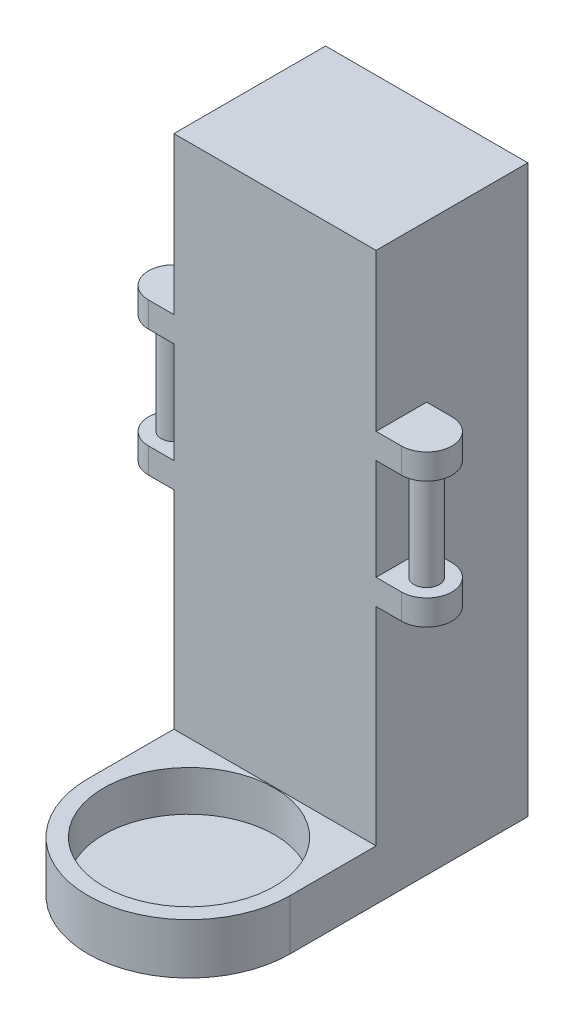
SolidWorks part; units mm, degrees
ref_plane "Front Plane" through (0, 0, 0) normal (0, 0, 1) x (1, 0, 0)
ref_plane "Top Plane" through (0, 0, 0) normal (0, 1, 0) x (1, 0, 0)
ref_plane "Right Plane" through (0, 0, 0) normal (1, 0, 0) x (0, 0, -1)
sketch "Sketch1" plane through (0, 0, 0) normal (0, 0, 1) x (1, 0, 0)
  line L1 (-25.4, -71.12) -> (25.4, -71.12)
  line L2 (-25.4, -71.12) -> (-25.4, 71.12)
  line L3 (-25.4, 71.12) -> (25.4, 71.12)
  line L4 (25.4, -71.12) -> (25.4, 71.12)
  line L5 (-25.4, -71.12) -> (25.4, 71.12) construction
  line L6 (-25.4, 71.12) -> (25.4, -71.12) construction
  point P0 (0, 0)
  dimension "D1" = 142.24
  dimension "D2" = 50.8
extrude "Boss-Extrude1" add sketch "Sketch1" along normal blind 38.1
sketch "Sketch8" plane through (0, -71.12, 0) normal (0, -1, 0) x (1, 0, 0)
  line L1 (-25.4, 38.1) -> (-25.4, 59.69)
  line L2 (25.4, 38.1) -> (25.4, 59.69)
  line L3 (-25.4, 38.1) -> (25.4, 38.1) construction
  line L4 (-25.4, 38.1) -> (25.4, 38.1)
  arc A0 (25.4, 59.69) -> (-25.4, 59.69) centre (0, 59.69) ccw
  circle A1 centre (0, 59.69) radius 21.4313
  dimension "D2" = 21.59
  dimension "D1" = 25.4
  dimension "D3" = 42.8625
extrude "Boss-Extrude2" add sketch "Sketch8" against normal blind 2.54 separate body contours L4 A1 L2 A0 L1 | A1 region at (-24.708, -71.12, 48.895) region at (0, -71.12, 59.69)
extrude "Boss-Extrude9" add sketch "Sketch8<5>" against normal blind 12.7 contours L2 A0 L1 L4 A1 region at (-24.708, -71.12, 48.895)
sketch "Sketch8<5>" plane through (0, -71.12, 0) normal (0, -1, 0) x (1, 0, 0) same geometry as "Sketch8"
sketch "Sketch18" plane through (0, 0, 38.1) normal (0, 0, 1) x (1, 0, 0)
  line L0 (0, -58.42) -> (0, 32.1084) construction
  line L1 (25.4, -58.42) -> (-25.4, -58.42) construction
sketch "Sketch19" plane through (-25.4, 0, 0) normal (-1, 0, 0) x (0, 0, 1)
  line L1 (38.1, 71.12) -> (38.1, -58.42) construction
  line L2 (38.1, -6.35) -> (38.1, 25.4) construction
  line L3 (38.1, 25.4) -> (25.4, 25.4)
  line L4 (25.4, 25.4) -> (25.4, 31.75)
  line L5 (25.4, 31.75) -> (38.1, 31.75)
  line L6 (38.1, 31.75) -> (38.1, 25.4)
  line L7 (25.4, -6.35) -> (25.4, 0)
  line L8 (25.4, 0) -> (38.1, 0)
  line L9 (38.1, 0) -> (38.1, -6.35)
  line L10 (38.1, -6.35) -> (25.4, -6.35)
  dimension "D1" = 12.7
  dimension "D2" = 25.4
  dimension "D3" = 6.35
extrude "Boss-Extrude10" add sketch "Sketch19" along normal blind 6.35
sketch "Sketch20" plane through (0, -6.35, 0) normal (0, -1, 0) x (1, 0, 0)
  line L0 (-31.75, 25.4) -> (-31.75, 38.1) construction
  line L1 (-31.75, 25.4) -> (-31.75, 38.1)
  arc A0 (-31.75, 38.1) -> (-31.75, 25.4) centre (-31.75, 31.75) ccw
extrude "Boss-Extrude11" add sketch "Sketch20" against normal blind 6.35
ref_plane "Plane1" through (0, 12.7, 0) normal (0, -1, 0) x (-1, 0, 0)
mirror "Mirror1" about plane through (0, 12.7, 0) normal (0, -1, 0) of "Boss-Extrude11"
sketch "Sketch23" plane through (0, 25.4, 0) normal (0, -1, 0) x (1, 0, 0)
  circle A2 centre (-31.75, 31.75) radius 3.175
  dimension "D1" = 6.35
extrude "Boss-Extrude12" add sketch "Sketch23" along normal up to surface (25.4 mm away) up to face at (-30.1625, 0, 31.75)
mirror "Mirror2" about plane through (0, 0, 0) normal (1, 0, 0) of "Boss-Extrude12", "Boss-Extrude11", "Boss-Extrude10", "Mirror1"
